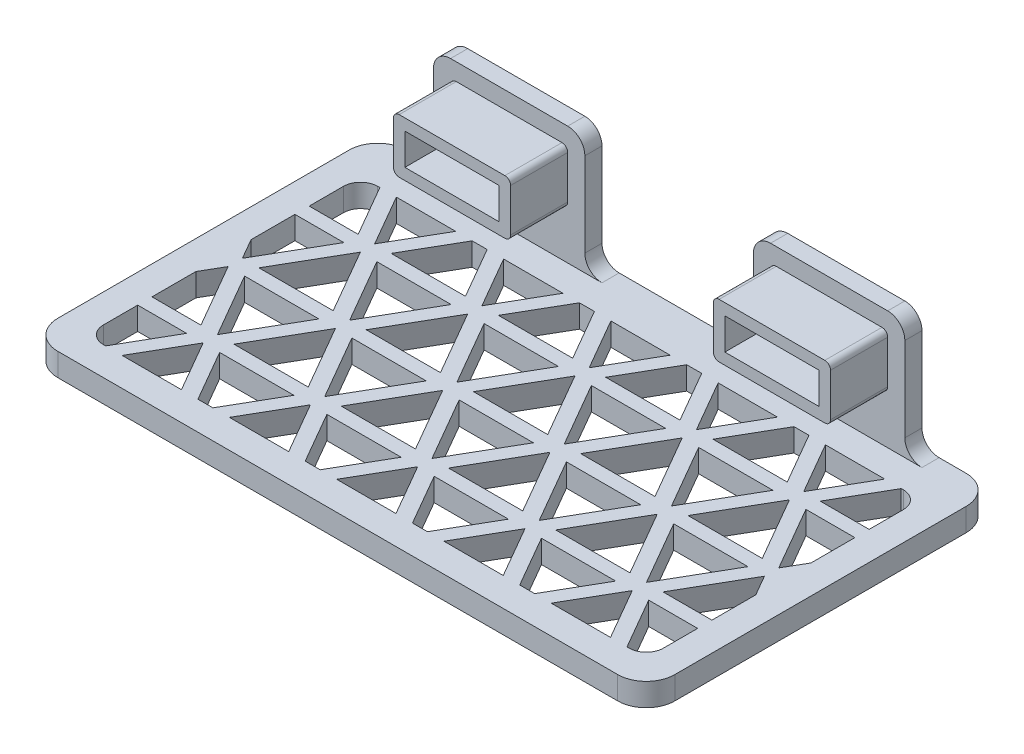
SolidWorks part; units mm, degrees
ref_plane "前视基准面" through (0, 0, 0) normal (0, 0, 1) x (1, 0, 0)
ref_plane "上视基准面" through (0, 0, 0) normal (0, 1, 0) x (1, 0, 0)
ref_plane "右视基准面" through (0, 0, 0) normal (1, 0, 0) x (0, 0, -1)
sketch "草图1" plane through (0, 0, 0) normal (0, 1, 0) x (1, 0, 0)
  line L1 (-54, -29) -> (54, -29)
  line L2 (-54, -29) -> (-54, 29)
  line L3 (-54, 29) -> (54, 29)
  line L4 (54, -29) -> (54, 29)
  line L5 (-54, -29) -> (54, 29) construction
  line L6 (-54, 29) -> (54, -29) construction
  point P0 (0, 0)
  dimension "D1" = 108
  dimension "D2" = 58
extrude "凸台-拉伸1" add sketch "草图1" along normal blind 4
sketch "草图2" plane through (0, 0, -29) normal (0, 0, -1) x (-1, 0, 0)
  line L0 (0, 0) -> (0, 35.8872) construction
  line L1 (-37.25, 21.75) -> (-18.75, 21.75)
  line L2 (-38.25, 20.75) -> (-38.25, 13.25)
  line L3 (-37.25, 12.25) -> (-18.75, 12.25)
  line L4 (-17.75, 20.75) -> (-17.75, 13.25)
  line L5 (17.75, 20.75) -> (17.75, 13.25)
  line L6 (37.25, 12.25) -> (18.75, 12.25)
  line L7 (38.25, 20.75) -> (38.25, 13.25)
  line L8 (37.25, 21.75) -> (18.75, 21.75)
  line L10 (-28, 21.75) -> (-28, 46.2565) construction
  line L11 (-38.25, 17) -> (-76.1792, 17) construction
  line L12 (-41.25, 21.75) -> (-41.25, 7)
  line L13 (-14.75, 21.75) -> (-14.75, 7)
  line L14 (-38.25, 24.75) -> (-17.75, 24.75)
  line L15 (38.25, 24.75) -> (17.75, 24.75)
  line L16 (-54, 0) -> (54, 0)
  line L17 (54, 0) -> (54, 4)
  line L18 (54, 4) -> (-54, 4)
  line L20 (-54, 0) -> (54, 0)
  line L22 (54, 4) -> (-54, 4)
  line L24 (14.75, 21.75) -> (14.75, 7)
  line L25 (41.25, 21.75) -> (41.25, 7)
  line L26 (-19.75, 19.75) -> (-19.75, 14.25)
  line L27 (-36.25, 14.25) -> (-19.75, 14.25)
  line L28 (-36.25, 19.75) -> (-36.25, 14.25)
  line L29 (-36.25, 19.75) -> (-19.75, 19.75)
  line L30 (54, 0) -> (54, 4)
  line L32 (-54, 4) -> (-54, 0)
  line L33 (-54, 4) -> (-54, 0)
  line L34 (36.25, 19.75) -> (19.75, 19.75)
  line L35 (36.25, 19.75) -> (36.25, 14.25)
  line L36 (36.25, 14.25) -> (19.75, 14.25)
  line L37 (19.75, 19.75) -> (19.75, 14.25)
  arc A0 (-18.75, 21.75) -> (-17.75, 20.75) centre (-18.75, 20.75) cw
  arc A1 (-38.25, 13.25) -> (-37.25, 12.25) centre (-37.25, 13.25) ccw
  arc A2 (-18.75, 12.25) -> (-17.75, 13.25) centre (-18.75, 13.25) ccw
  arc A3 (-37.25, 21.75) -> (-38.25, 20.75) centre (-37.25, 20.75) ccw
  arc A4 (37.25, 21.75) -> (38.25, 20.75) centre (37.25, 20.75) cw
  arc A5 (18.75, 12.25) -> (17.75, 13.25) centre (18.75, 13.25) cw
  arc A6 (38.25, 13.25) -> (37.25, 12.25) centre (37.25, 13.25) cw
  arc A7 (18.75, 21.75) -> (17.75, 20.75) centre (18.75, 20.75) ccw
  arc A8 (-41.25, 7) -> (-44.25, 4) centre (-44.25, 7) cw
  arc A9 (-14.75, 7) -> (-11.75, 4) centre (-11.75, 7) ccw
  arc A10 (-41.25, 21.75) -> (-38.25, 24.75) centre (-38.25, 21.75) cw
  arc A11 (-14.75, 21.75) -> (-17.75, 24.75) centre (-17.75, 21.75) ccw
  arc A12 (41.25, 21.75) -> (38.25, 24.75) centre (38.25, 21.75) ccw
  arc A13 (14.75, 21.75) -> (17.75, 24.75) centre (17.75, 21.75) cw
  arc A14 (14.75, 7) -> (11.75, 4) centre (11.75, 7) cw
  arc A15 (41.25, 7) -> (44.25, 4) centre (44.25, 7) ccw
  arc A16 (-19.75, 14.25) -> (-19.75, 14.25) centre (-19.75, 14.25) ccw
  arc A17 (-36.25, 14.25) -> (-36.25, 14.25) centre (-36.25, 14.25) ccw
  arc A18 (-36.25, 19.75) -> (-36.25, 19.75) centre (-36.25, 19.75) ccw
  arc A19 (-19.75, 19.75) -> (-19.75, 19.75) centre (-19.75, 19.75) cw
  point P45 (-41.25, 24.75)
  point P48 (-14.75, 24.75)
  line M16 (-54, 0) -> (54, 0)
  line M17 (54, 0) -> (54, 4)
  line M18 (54, 4) -> (-54, 4)
  line M19 (-54, 4) -> (-54, 0)
  dimension "D1" = 1
  dimension "D7" = 3
  dimension "D10" = 3
  dimension "D2" = 9.5
  dimension "D3" = 20.5
  dimension "D4" = 28
  dimension "D5" = 17
  dimension "D8" = 3
  dimension "D9" = 3
  dimension "D11" = 2
  dimension "D6" = 0
extrude "凸台-拉伸2" add sketch "草图2" along normal blind 3 contours L1 A3 L2 A1 L3 A2 L4 A0 | L13 A11 L14 A10 L12 A8 L22 A9 A3 L1 A0 L4 A2 L3 A1 L2 | L22 M19 M16 M17 M18 | A15 L25 A12 L15 A13 L24 A14 L22 A7 L8 A4 L7 A6 L6 A5 L5 | L8 A7 L5 A5 L6 A6 L7 A4 region at (28, 21.5241, -29) region at (-18.2027, 21.2973, -29) region at (40.0987, 23.5987, -29) region at (0, 2, -29) region at (-14.144, 4.606, -29)
extrude "凸台-拉伸3" add sketch "草图2<3>" against normal blind 10 contours L1 A3 L2 A1 L3 A2 L4 A0 | L8 A7 L5 A5 L6 A6 L7 A4 region at (28, 21.5241, -29) region at (-18.2027, 21.2973, -29)
sketch "草图2<3>" plane through (0, 0, -29) normal (0, 0, -1) x (-1, 0, 0) same geometry as "草图2"
fillet "圆角1" radius 5 4 edges at (-54, 2, -32) (-54, 2, 29) (54, 2, 29) (54, 2, -32)
sketch "草图3" plane through (0, 0, 0) normal (0, -1, 0) x (1, 0, 0)
  line L4 (-49, 29) -> (49, 29) construction
  line L5 (-46, -24) -> (46, -24)
  line L6 (-49, -21) -> (-49, 21)
  line L7 (-46, 24) -> (46, 24)
  line L12 (49, -21) -> (49, 21)
  line L13 (-49, -24) -> (49, 24) construction
  line L14 (-49, 24) -> (49, -24) construction
  line L15 (54, 24) -> (54, -27) construction
  line L16 (0, 0) -> (114.3325, 0) construction
  line L17 (0, 0) -> (0, 80.0939) construction
  line L18 (0, 12.5083) -> (-6.5, 1.25)
  line L19 (0, 12.5083) -> (6.5, 1.25)
  line L20 (6.5, 1.25) -> (-6.5, 1.25)
  line L21 (18.7735, 12.5083) -> (12.2735, 1.25)
  line L22 (18.7735, 12.5083) -> (25.2735, 1.25)
  line L23 (25.2735, 1.25) -> (12.2735, 1.25)
  line L24 (37.547, 12.5083) -> (31.047, 1.25)
  line L25 (37.547, 12.5083) -> (44.047, 1.25)
  line L26 (44.047, 1.25) -> (31.047, 1.25)
  line L30 (-18.7735, 12.5083) -> (-25.2735, 1.25)
  line L31 (-18.7735, 12.5083) -> (-12.2735, 1.25)
  line L32 (-12.2735, 1.25) -> (-25.2735, 1.25)
  line L33 (-37.547, 12.5083) -> (-44.047, 1.25)
  line L34 (-37.547, 12.5083) -> (-31.047, 1.25)
  line L35 (-31.047, 1.25) -> (-44.047, 1.25)
  line L42 (-31.047, -1.25) -> (-44.047, -1.25)
  line L43 (-37.547, -12.5083) -> (-31.047, -1.25)
  line L44 (-37.547, -12.5083) -> (-44.047, -1.25)
  line L45 (-12.2735, -1.25) -> (-25.2735, -1.25)
  line L46 (-18.7735, -12.5083) -> (-12.2735, -1.25)
  line L47 (-18.7735, -12.5083) -> (-25.2735, -1.25)
  line L51 (44.047, -1.25) -> (31.047, -1.25)
  line L52 (37.547, -12.5083) -> (44.047, -1.25)
  line L53 (37.547, -12.5083) -> (31.047, -1.25)
  line L54 (25.2735, -1.25) -> (12.2735, -1.25)
  line L55 (18.7735, -12.5083) -> (25.2735, -1.25)
  line L56 (18.7735, -12.5083) -> (12.2735, -1.25)
  line L57 (6.5, -1.25) -> (-6.5, -1.25)
  line L58 (0, -12.5083) -> (6.5, -1.25)
  line L59 (0, -12.5083) -> (-6.5, -1.25)
  line L60 (2.8868, 12.5083) -> (9.3868, 1.25)
  line L61 (9.3868, 1.25) -> (15.8868, 12.5083)
  line L62 (2.8868, 12.5083) -> (15.8868, 12.5083)
  line L63 (21.6603, 12.5083) -> (34.6603, 12.5083)
  line L64 (-56.3205, 12.5083) -> (-62.8205, 1.25) [skipped]
  line L65 (-56.3205, 12.5083) -> (-49.8205, 1.25) [skipped]
  line L66 (-49.8205, 1.25) -> (-62.8205, 1.25) [skipped]
  line L67 (56.3205, 12.5083) -> (49.8205, 1.25) [skipped]
  line L68 (56.3205, 12.5083) -> (62.8205, 1.25) [skipped]
  line L69 (62.8205, 1.25) -> (49.8205, 1.25) [skipped]
  line L70 (21.6603, 12.5083) -> (28.1603, 1.25)
  line L71 (28.1603, 1.25) -> (34.6603, 12.5083)
  line L72 (40.4338, 12.5083) -> (53.4338, 12.5083)
  line L73 (40.4338, 12.5083) -> (46.9338, 1.25)
  line L74 (46.9338, 1.25) -> (53.4338, 12.5083)
  line L75 (28.1603, 12.5083) -> (28.1603, 1.25) construction
  line L76 (-46.9338, 1.25) -> (-53.4338, 12.5083)
  line L77 (-40.4338, 12.5083) -> (-53.4338, 12.5083)
  line L78 (-40.4338, 12.5083) -> (-46.9338, 1.25)
  line L79 (-28.1603, 1.25) -> (-34.6603, 12.5083)
  line L80 (-21.6603, 12.5083) -> (-34.6603, 12.5083)
  line L81 (-21.6603, 12.5083) -> (-28.1603, 1.25)
  line L82 (-9.3868, 1.25) -> (-15.8868, 12.5083)
  line L83 (-2.8868, 12.5083) -> (-15.8868, 12.5083)
  line L84 (-2.8868, 12.5083) -> (-9.3868, 1.25)
  line L85 (46.9338, -1.25) -> (53.4338, -12.5083)
  line L86 (40.4338, -12.5083) -> (53.4338, -12.5083)
  line L87 (40.4338, -12.5083) -> (46.9338, -1.25)
  line L88 (21.6603, -12.5083) -> (28.1603, -1.25)
  line L89 (28.1603, -1.25) -> (34.6603, -12.5083)
  line L90 (21.6603, -12.5083) -> (34.6603, -12.5083)
  line L91 (-2.8868, -12.5083) -> (-9.3868, -1.25)
  line L92 (2.8868, -12.5083) -> (9.3868, -1.25)
  line L93 (2.8868, -12.5083) -> (15.8868, -12.5083)
  line L94 (9.3868, -1.25) -> (15.8868, -12.5083)
  line L95 (-9.3868, -1.25) -> (-15.8868, -12.5083)
  line L96 (-2.8868, -12.5083) -> (-15.8868, -12.5083)
  line L97 (-21.6603, -12.5083) -> (-34.6603, -12.5083)
  line L98 (-21.6603, -12.5083) -> (-28.1603, -1.25)
  line L99 (-28.1603, -1.25) -> (-34.6603, -12.5083)
  line L100 (-40.4338, -12.5083) -> (-53.4338, -12.5083)
  line L101 (-46.9338, -1.25) -> (-53.4338, -12.5083)
  line L102 (-40.4338, -12.5083) -> (-46.9338, -1.25)
  line L103 (-56.7075, 13.7583) -> (62.8861, 13.7583) construction
  line L104 (28.1603, 15.0083) -> (28.1603, 26.2667) construction
  line L105 (-2.8868, 15.0083) -> (-9.3868, 26.2667)
  line L106 (-2.8868, 15.0083) -> (-15.8868, 15.0083)
  line L107 (-9.3868, 26.2667) -> (-15.8868, 15.0083)
  line L108 (-21.6603, 15.0083) -> (-28.1603, 26.2667)
  line L109 (-21.6603, 15.0083) -> (-34.6603, 15.0083)
  line L110 (-28.1603, 26.2667) -> (-34.6603, 15.0083)
  line L111 (-40.4338, 15.0083) -> (-46.9338, 26.2667)
  line L112 (-40.4338, 15.0083) -> (-53.4338, 15.0083)
  line L113 (-46.9338, 26.2667) -> (-53.4338, 15.0083)
  line L114 (46.9338, 26.2667) -> (53.4338, 15.0083)
  line L115 (40.4338, 15.0083) -> (46.9338, 26.2667)
  line L116 (40.4338, 15.0083) -> (53.4338, 15.0083)
  line L117 (28.1603, 26.2667) -> (34.6603, 15.0083)
  line L118 (21.6603, 15.0083) -> (28.1603, 26.2667)
  line L119 (21.6603, 15.0083) -> (34.6603, 15.0083)
  line L120 (2.8868, 15.0083) -> (15.8868, 15.0083)
  line L121 (9.3868, 26.2667) -> (15.8868, 15.0083)
  line L122 (2.8868, 15.0083) -> (9.3868, 26.2667)
  line L123 (-31.047, 26.2667) -> (-44.047, 26.2667)
  line L124 (-37.547, 15.0083) -> (-31.047, 26.2667)
  line L125 (-37.547, 15.0083) -> (-44.047, 26.2667)
  line L126 (-12.2735, 26.2667) -> (-25.2735, 26.2667)
  line L127 (-18.7735, 15.0083) -> (-12.2735, 26.2667)
  line L128 (-18.7735, 15.0083) -> (-25.2735, 26.2667)
  line L129 (44.047, 26.2667) -> (31.047, 26.2667)
  line L130 (37.547, 15.0083) -> (44.047, 26.2667)
  line L131 (37.547, 15.0083) -> (31.047, 26.2667)
  line L132 (25.2735, 26.2667) -> (12.2735, 26.2667)
  line L133 (18.7735, 15.0083) -> (25.2735, 26.2667)
  line L134 (18.7735, 15.0083) -> (12.2735, 26.2667)
  line L135 (6.5, 26.2667) -> (-6.5, 26.2667)
  line L136 (0, 15.0083) -> (6.5, 26.2667)
  line L137 (0, 15.0083) -> (-6.5, 26.2667)
  line L138 (28.1603, -15.0083) -> (28.1603, -26.2667) construction
  line L139 (0, -15.0083) -> (-6.5, -26.2667)
  line L140 (0, -15.0083) -> (6.5, -26.2667)
  line L141 (6.5, -26.2667) -> (-6.5, -26.2667)
  line L142 (18.7735, -15.0083) -> (12.2735, -26.2667)
  line L143 (18.7735, -15.0083) -> (25.2735, -26.2667)
  line L144 (25.2735, -26.2667) -> (12.2735, -26.2667)
  line L145 (37.547, -15.0083) -> (31.047, -26.2667)
  line L146 (37.547, -15.0083) -> (44.047, -26.2667)
  line L147 (44.047, -26.2667) -> (31.047, -26.2667)
  line L148 (-18.7735, -15.0083) -> (-25.2735, -26.2667)
  line L149 (-18.7735, -15.0083) -> (-12.2735, -26.2667)
  line L150 (-12.2735, -26.2667) -> (-25.2735, -26.2667)
  line L151 (-37.547, -15.0083) -> (-44.047, -26.2667)
  line L152 (-37.547, -15.0083) -> (-31.047, -26.2667)
  line L153 (-31.047, -26.2667) -> (-44.047, -26.2667)
  line L154 (2.8868, -15.0083) -> (9.3868, -26.2667)
  line L155 (9.3868, -26.2667) -> (15.8868, -15.0083)
  line L156 (2.8868, -15.0083) -> (15.8868, -15.0083)
  line L157 (21.6603, -15.0083) -> (34.6603, -15.0083)
  line L158 (21.6603, -15.0083) -> (28.1603, -26.2667)
  line L159 (28.1603, -26.2667) -> (34.6603, -15.0083)
  line L160 (40.4338, -15.0083) -> (53.4338, -15.0083)
  line L161 (40.4338, -15.0083) -> (46.9338, -26.2667)
  line L162 (46.9338, -26.2667) -> (53.4338, -15.0083)
  line L163 (-46.9338, -26.2667) -> (-53.4338, -15.0083)
  line L164 (-40.4338, -15.0083) -> (-53.4338, -15.0083)
  line L165 (-40.4338, -15.0083) -> (-46.9338, -26.2667)
  line L166 (-28.1603, -26.2667) -> (-34.6603, -15.0083)
  line L167 (-21.6603, -15.0083) -> (-34.6603, -15.0083)
  line L168 (-21.6603, -15.0083) -> (-28.1603, -26.2667)
  line L169 (-9.3868, -26.2667) -> (-15.8868, -15.0083)
  line L170 (-2.8868, -15.0083) -> (-15.8868, -15.0083)
  line L171 (-2.8868, -15.0083) -> (-9.3868, -26.2667)
  line L172 (-46, -24) -> (46, -24)
  arc A4 (46, -24) -> (49, -21) centre (46, -21) ccw
  arc A5 (-49, 21) -> (-46, 24) centre (-46, 21) cw
  arc A6 (-46, -24) -> (-49, -21) centre (-46, -21) cw
  arc A7 (46, 24) -> (49, 21) centre (46, 21) cw
  arc A8 (46, -24) -> (49, -21) centre (46, -21) ccw
  arc A9 (-49, -21) -> (-46, -24) centre (-46, -21) ccw
  point P0 (0, 0)
  point P35 (22.0235, 6.8792)
  point P39 (-18.7735, 0)
  point P43 (-37.547, 0)
  point P48 (-56.3205, 0)
  dimension "D3" = 3
  dimension "D1" = 5
  dimension "D2" = 5
  dimension "D4" = 60
  dimension "D5" = 13
  dimension "D8" = 2.5
  dimension "D9" = 2.5
  dimension "D10" = 2.5
  dimension "D11" = 3
  dimension "D12" = 2.5
  dimension "D6" = 4
  dimension "D7" = 4
extrude "切除-拉伸1" cut sketch "草图3" against normal up to next (4 mm away) contours A5 L6 L112 L111 L7 | L125 L124 L7 | L7 L110 L109 L108 | L128 L127 L7 | L7 L107 L106 L105 | L137 L136 L7 | L122 L120 L121 L7 | L134 L133 L7 | L118 L119 L117 L7 | L131 L130 L7 | A7 L7 L115 L116 L12 | L73 L74 L12 L72 | L26 L25 L24 | L70 L71 L63 | L23 L22 L21 | L62 L60 L61 | L20 L19 L18 | L84 L83 L82 | L32 L31 L30 | L81 L80 L79 | L35 L34 L33 | L78 L77 L6 L76 | L100 L102 L101 L6 | L44 L43 L42 | A6 L5 L165 L164 L6 | L152 L151 L5 | L98 L99 L97 | L168 L167 L166 L5 | L47 L46 L45 | L171 L170 L169 L5 | L149 L148 L5 | L96 L91 L95 | L59 L58 L57 | L156 L154 L5 L155 | L94 L92 L93 | L56 L55 L54 | L5 L159 L157 L158 | L88 L90 L89 | L53 L52 L51 | L140 L139 L5 | L143 L142 L5 | L146 L145 L5 | L87 L86 L12 L85 | L5 A4 L12 L160 L161 region at (-45.7332, 0, -18.6856) region at (-37.547, 0, -21.0028) region at (-45.8593, 0, -8.3939) region at (-28.1603, 0, -18.5079) region at (-45.8593, 0, 8.3939) region at (-18.7735, 0, -21.0028) region at (-45.7332, 0, 18.6856) region at (-9.3868, 0, -18.5079) region at (0, 0, -21.0028) region at (-37.547, 0, 21.0028) region at (9.3868, 0, -18.5079) region at (-28.1603, 0, 18.5079) region at (18.7735, 0, -21.0028) region at (-18.7735, 0, 21.0028) region at (28.1603, 0, -18.5079) region at (-9.3868, 0, 18.5079) region at (37.547, 0, -21.0028) region at (0, 0, 21.0028) region at (45.7332, 0, -18.6856) region at (9.3868, 0, 18.5079) region at (18.7735, 0, 21.0028) region at (45.8593, 0, -8.3939) region at (28.1603, 0, 18.5079) region at (45.8593, 0, 8.3939) region at (37.547, 0, 21.0028) region at (45.7332, 0, 18.6856) region at (0, 0, 5.0028) region at (18.7735, 0, 5.0028) region at (37.547, 0, 5.0028) region at (-18.7735, 0, 5.0028) region at (-37.547, 0, 5.0028) region at (-37.547, 0, -5.0028) region at (-18.7735, 0, -5.0028) region at (37.547, 0, -5.0028) region at (18.7735, 0, -5.0028) region at (0, 0, -5.0028) region at (9.3868, 0, 8.7556) region at (28.1603, 0, 8.7556) region at (-28.1603, 0, 8.7556) region at (-9.3868, 0, 8.7556) region at (28.1603, 0, -8.7556) region at (-9.3868, 0, -8.7556) region at (9.3868, 0, -8.7556) region at (-28.1603, 0, -8.7556)
